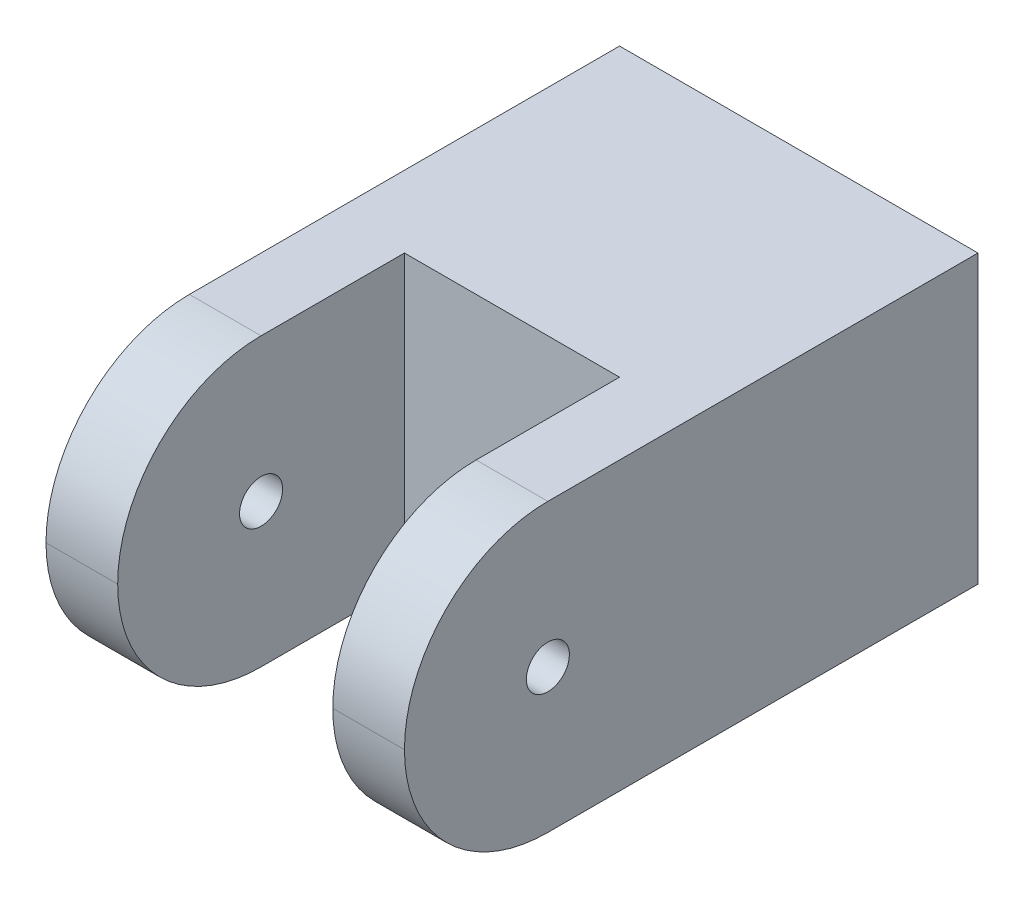
SolidWorks part; units mm, degrees
ref_plane "Alzado" through (0, 0, 0) normal (0, 0, 1) x (1, 0, 0)
ref_plane "Planta" through (0, 0, 0) normal (0, 1, 0) x (1, 0, 0)
ref_plane "Vista lateral" through (0, 0, 0) normal (1, 0, 0) x (0, 0, -1)
sketch "Sketch1" plane through (0, 0, 0) normal (0, 0, 1) x (1, 0, 0)
  line L1 (-12.5, 10) -> (12.5, 10)
  line L2 (-12.5, 10) -> (-12.5, -10)
  line L3 (-12.5, -10) -> (12.5, -10)
  line L4 (12.5, 10) -> (12.5, -10)
  dimension "D1" = 20
  dimension "D2" = 25
  dimension "D3" = 12.5
  dimension "D4" = 10
extrude "Boss-Extrude1" add sketch "Sketch1" along normal blind 40 contours L1 L4 L3 L2
sketch "Sketch2" plane through (0, 0, 40) normal (0, 0, 1) x (1, 0, 0)
  line L0 (-12.5, 10) -> (12.5, 10) construction
  line L1 (-7.5, 10) -> (7.5, 10)
  line L2 (-7.5, 10) -> (-7.5, -10)
  line L3 (-7.5, -10) -> (7.5, -10)
  line L4 (7.5, 10) -> (7.5, -10)
  line L5 (-12.5, -10) -> (12.5, -10) construction
  line L6 (-12.5, 10) -> (-12.5, -10) construction
  dimension "D1" = 5
  dimension "D2" = 15
extrude "Cut-Extrude1" cut sketch "Sketch2" against normal blind 20
sketch "Sketch3" plane through (12.5, 0, 0) normal (1, 0, 0) x (0, 0, -1)
  line L0 (-40, 10) -> (-40, -10) construction
  line L1 (-40, -10) -> (0, -10) construction
  circle A0 centre (-30, 0) radius 1.5
  dimension "D1" = 3
  dimension "D2" = 10
  dimension "D3" = 10
extrude "Cut-Extrude2" cut sketch "Sketch3" against normal blind 30
fillet "Fillet1" radius 10 4 edges at (-10, 10, 40) (10, 10, 40) (10, -10, 40) (-10, -10, 40)
sketch "Sketch4" plane through (0, 0, 20) normal (0, 0, 1) x (1, 0, 0)
  line L0 (-7.5, -10) -> (7.5, -10) construction
  line L1 (7.5, -10) -> (7.5, 10) construction
  circle A0 centre (0, -7) radius 1.5
  dimension "D1" = 3
  dimension "D2" = 3
  dimension "D3" = 7.5
extrude "Cut-Extrude3" cut sketch "Sketch4" against normal blind 20
fillet "Fillet2" radius 1 1 edges at (1.5, -7, 20)
sketch "Sketch5" plane through (0, 0, 20) normal (0, 0, 1) x (1, 0, 0)
  line L0 (-7.5, -10) -> (7.5, -10) construction
  line L1 (-3, -2) -> (3, -2)
  line L3 (-3, -4) -> (3, -4)
  line L6 (-7.5, 10) -> (-7.5, -10) construction
  arc A0 (-3, -2) -> (-3, -4) centre (-3, -3) ccw
  arc A1 (3, -4) -> (3, -2) centre (3, -3) ccw
  dimension "D1" = 1
  dimension "D2" = 1
  dimension "D3" = 8
  dimension "D4" = 4.5
  dimension "D5" = 6
extrude "Cut-Extrude4" cut sketch "Sketch5" against normal blind 20
